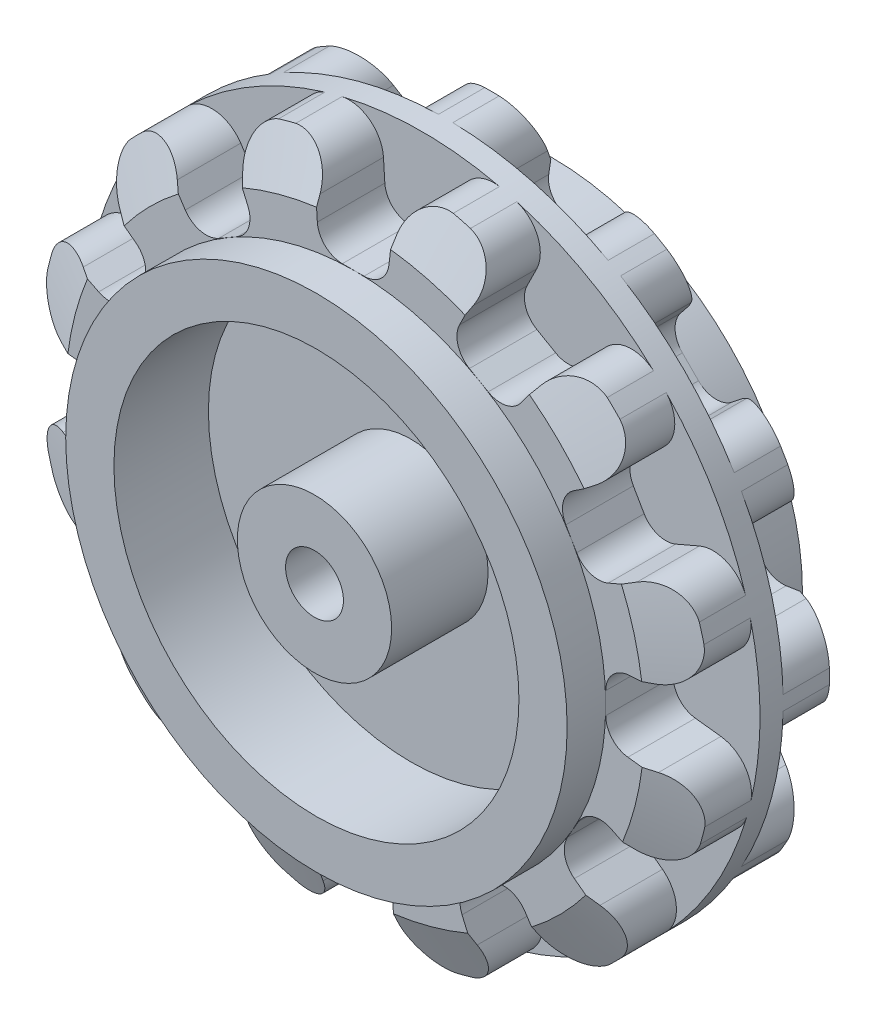
SolidWorks part; units mm, degrees
ref_plane "Plan de face" through (0, 0, 0) normal (0, 0, 1) x (1, 0, 0)
ref_plane "Plan de dessus" through (0, 0, 0) normal (0, 1, 0) x (1, 0, 0)
ref_plane "Plan de droite" through (0, 0, 0) normal (1, 0, 0) x (0, 0, -1)
sketch "Esquisse2" plane through (0, 0, 0) normal (0, 1, 0) x (1, 0, 0)
  line L0 (0, 0) -> (0, 3425.2641) construction
  line L1 (-17.5, -1.958) -> (-1.5, -1.958) construction
  line L2 (-17.5, -4.958) -> (-17.5, 1.042)
  line L3 (-17.5, 1.042) -> (-15, 2.142)
  line L4 (-15, 2.142) -> (-13, 2.142)
  line L5 (-13, 2.142) -> (-13, 4.142)
  line L6 (-13, 4.142) -> (-10.5, 4.142)
  line L7 (-10.5, 4.142) -> (-10.5, -0.758)
  line L8 (-10.5, -0.758) -> (-4, -0.758)
  line L9 (-1.5, -0.758) -> (-1.5, -3.158)
  line L10 (-10.5, -3.158) -> (-4, -3.158)
  line L11 (-10.5, -8.058) -> (-10.5, -3.158)
  line L12 (-13, -8.058) -> (-10.5, -8.058)
  line L13 (-13, -6.058) -> (-13, -8.058)
  line L14 (-15, -6.058) -> (-13, -6.058)
  line L15 (-17.5, -4.958) -> (-15, -6.058)
  line L16 (-1.5, -0.758) -> (-1.5, -0.058)
  line L17 (-1.5, -0.058) -> (-4, -0.058)
  line L18 (-4, -0.058) -> (-4, -0.758)
  line L19 (-1.5, -3.158) -> (-1.5, -8.158)
  line L20 (-1.5, -8.158) -> (-4, -8.158)
  line L21 (-4, -8.158) -> (-4, -3.158)
  dimension "D1" = 1.5
  dimension "D2" = 10.5
  dimension "D3" = 17.5
  dimension "D4" = 2
  dimension "D5" = 2.5
  dimension "D6" = 1.2
  dimension "D7" = 3
  dimension "D8" = 4.1
  dimension "D9" = 2
  dimension "D10" = 4.9
  dimension "D11" = 2.5
  dimension "D12" = 0.7
  dimension "D13" = 2.5
  dimension "D14" = 5
revolve "Révolution1" add sketch "Esquisse2" angle 360 about L0
sketch "Esquisse3" plane through (0, 0, 6.058) normal (0, 0, 1) x (1, 0, 0)
  line L0 (0, 0) -> (0, 50000) construction
  line L1 (0, 0) -> (4.5293, 16.9037) construction
  line L2 (0, 0) -> (-4.5293, 16.9037) construction
  line L3 (-0.655, 13) -> (0.4677, 13)
  line L4 (-2.3132, 17.3932) -> (2.1868, 17.3932) construction
  line L5 (-4.5293, 16.9037) -> (-4.2854, 16.9691)
  line L6 (4.5293, 16.9037) -> (4.1678, 17.0006)
  line L7 (-1.9525, 14.2186) -> (-2.023, 15.3431)
  line L8 (1.9142, 15.4718) -> (1.7588, 14.1484)
  line L9 (-4.9465, 18.4605) -> (-12940.9449, 48296.2637) construction
  line L10 (5.9327, 11.5858) -> (6.905, 11.0245)
  line L11 (4.5293, 16.9037) -> (4.7733, 16.8383)
  line L12 (-4.9465, 18.4605) -> (4.9465, 18.4605)
  line L13 (-4.5293, 16.9037) -> (-4.9465, 18.4605)
  line L14 (-4.5293, 16.9037) -> (-2.1608, 17.5384) construction
  line L15 (4.5293, 16.9037) -> (2.2281, 17.5203) construction
  line L16 (2.2281, 17.5203) -> (1.9142, 15.4718) construction
  line L17 (-2.023, 15.3431) -> (-2.1608, 17.5384) construction
  line L18 (12.3744, 12.3744) -> (12.1097, 12.639)
  line L19 (5.4184, 13.2899) -> (5.9196, 14.2991)
  line L20 (9.3937, 12.4419) -> (8.5974, 11.3735)
  line L21 (4.9465, 18.4605) -> (13.514, 13.514)
  line L22 (4.9465, 18.4605) -> (12940.9192, 48296.1679) construction
  line L23 (4.5293, 16.9037) -> (4.9465, 18.4605)
  line L24 (4.5293, 16.9037) -> (4.9465, 18.4605)
  line L25 (12.3744, 12.3744) -> (13.514, 13.514)
  line L26 (10.9308, 7.0673) -> (11.4922, 6.095)
  line L27 (12.3744, 12.3744) -> (12.5529, 12.1958)
  line L28 (16.9037, 4.5293) -> (16.8068, 4.8908)
  line L29 (11.3374, 8.8002) -> (12.276, 9.4236)
  line L30 (14.3561, 6.0781) -> (13.1323, 5.551)
  line L31 (13.514, 13.514) -> (18.4605, 4.9465)
  line L32 (12.3744, 12.3744) -> (13.514, 13.514)
  line L33 (16.9037, 4.5293) -> (18.4605, 4.9465)
  line L34 (13, 0.655) -> (13, -0.4677)
  line L35 (16.9037, 4.5293) -> (16.9691, 4.2854)
  line L36 (16.9037, -4.5293) -> (17.0006, -4.1678)
  line L37 (14.2186, 1.9525) -> (15.3431, 2.023)
  line L38 (15.4718, -1.9142) -> (14.1484, -1.7588)
  line L39 (18.4605, 4.9465) -> (18.4605, -4.9465)
  line L40 (16.9037, 4.5293) -> (18.4605, 4.9465)
  line L41 (16.9037, -4.5293) -> (18.4605, -4.9465)
  line L42 (11.5858, -5.9327) -> (11.0245, -6.905)
  line L43 (16.9037, -4.5293) -> (16.8383, -4.7733)
  line L44 (12.3744, -12.3744) -> (12.639, -12.1097)
  line L45 (13.2899, -5.4184) -> (14.2991, -5.9196)
  line L46 (12.4419, -9.3937) -> (11.3735, -8.5974)
  line L47 (18.4605, -4.9465) -> (13.514, -13.514)
  line L48 (16.9037, -4.5293) -> (18.4605, -4.9465)
  line L49 (12.3744, -12.3744) -> (13.514, -13.514)
  line L50 (7.0673, -10.9308) -> (6.095, -11.4922)
  line L51 (12.3744, -12.3744) -> (12.1958, -12.5529)
  line L52 (4.5293, -16.9037) -> (4.8908, -16.8068)
  line L53 (8.8002, -11.3374) -> (9.4236, -12.276)
  line L54 (6.0781, -14.3561) -> (5.551, -13.1323)
  line L55 (13.514, -13.514) -> (4.9465, -18.4605)
  line L56 (12.3744, -12.3744) -> (13.514, -13.514)
  line L57 (4.5293, -16.9037) -> (4.9465, -18.4605)
  line L58 (0.655, -13) -> (-0.4677, -13)
  line L59 (4.5293, -16.9037) -> (4.2854, -16.9691)
  line L60 (-4.5293, -16.9037) -> (-4.1678, -17.0006)
  line L61 (1.9525, -14.2186) -> (2.023, -15.3431)
  line L62 (-1.9142, -15.4718) -> (-1.7588, -14.1484)
  line L63 (4.9465, -18.4605) -> (-4.9465, -18.4605)
  line L64 (4.5293, -16.9037) -> (4.9465, -18.4605)
  line L65 (-4.5293, -16.9037) -> (-4.9465, -18.4605)
  line L66 (-5.9327, -11.5858) -> (-6.905, -11.0245)
  line L67 (-4.5293, -16.9037) -> (-4.7733, -16.8383)
  line L68 (-12.3744, -12.3744) -> (-12.1097, -12.639)
  line L69 (-5.4184, -13.2899) -> (-5.9196, -14.2991)
  line L70 (-9.3937, -12.4419) -> (-8.5974, -11.3735)
  line L71 (-4.9465, -18.4605) -> (-13.514, -13.514)
  line L72 (-4.5293, -16.9037) -> (-4.9465, -18.4605)
  line L73 (-12.3744, -12.3744) -> (-13.514, -13.514)
  line L74 (-10.9308, -7.0673) -> (-11.4922, -6.095)
  line L75 (-12.3744, -12.3744) -> (-12.5529, -12.1958)
  line L76 (-16.9037, -4.5293) -> (-16.8068, -4.8908)
  line L77 (-11.3374, -8.8002) -> (-12.276, -9.4236)
  line L78 (-14.3561, -6.0781) -> (-13.1323, -5.551)
  line L79 (-13.514, -13.514) -> (-18.4605, -4.9465)
  line L80 (-12.3744, -12.3744) -> (-13.514, -13.514)
  line L81 (-16.9037, -4.5293) -> (-18.4605, -4.9465)
  line L82 (-13, -0.655) -> (-13, 0.4677)
  line L83 (-16.9037, -4.5293) -> (-16.9691, -4.2854)
  line L84 (-16.9037, 4.5293) -> (-17.0006, 4.1678)
  line L85 (-14.2186, -1.9525) -> (-15.3431, -2.023)
  line L86 (-15.4718, 1.9142) -> (-14.1484, 1.7588)
  line L87 (-18.4605, -4.9465) -> (-18.4605, 4.9465)
  line L88 (-16.9037, -4.5293) -> (-18.4605, -4.9465)
  line L89 (-16.9037, 4.5293) -> (-18.4605, 4.9465)
  line L90 (-11.5858, 5.9327) -> (-11.0245, 6.905)
  line L91 (-16.9037, 4.5293) -> (-16.8383, 4.7733)
  line L92 (-12.3744, 12.3744) -> (-12.639, 12.1097)
  line L93 (-13.2899, 5.4184) -> (-14.2991, 5.9196)
  line L94 (-12.4419, 9.3937) -> (-11.3735, 8.5974)
  line L95 (-18.4605, 4.9465) -> (-13.514, 13.514)
  line L96 (-16.9037, 4.5293) -> (-18.4605, 4.9465)
  line L97 (-12.3744, 12.3744) -> (-13.514, 13.514)
  line L98 (-7.0673, 10.9308) -> (-6.095, 11.4922)
  line L99 (-12.3744, 12.3744) -> (-12.1958, 12.5529)
  line L100 (-4.5293, 16.9037) -> (-4.8908, 16.8068)
  line L101 (-8.8002, 11.3374) -> (-9.4236, 12.276)
  line L102 (-6.0781, 14.3561) -> (-5.551, 13.1323)
  line L103 (-13.514, 13.514) -> (-4.9465, 18.4605)
  line L104 (-12.3744, 12.3744) -> (-13.514, 13.514)
  line L105 (-4.5293, 16.9037) -> (-4.9465, 18.4605)
  arc A0 (4.1678, 17.0006) -> (1.9142, 15.4718) centre (3.7019, 15.2619) ccw
  arc A1 (-2.023, 15.3431) -> (-4.2854, 16.9691) centre (-3.8195, 15.2304) ccw
  circle A4 centre (0, 0) radius 15 construction
  arc A5 (12.1097, 12.639) -> (9.3937, 12.4419) centre (10.8369, 11.3662) ccw
  arc A6 (5.9196, 14.2991) -> (4.7733, 16.8383) centre (4.3074, 15.0997) ccw
  arc A7 (8.5974, 11.3735) -> (6.905, 11.0245) centre (7.555, 12.1503) cw
  arc A8 (5.9327, 11.5858) -> (5.4184, 13.2899) centre (6.5827, 12.7117) cw
  arc A9 (16.8068, 4.8908) -> (14.3561, 6.0781) centre (15.0682, 4.425) ccw
  arc A10 (12.276, 9.4236) -> (12.5529, 12.1958) centre (11.2802, 10.923) ccw
  arc A11 (13.1323, 5.551) -> (11.4922, 6.095) centre (12.618, 6.745) cw
  arc A12 (10.9308, 7.0673) -> (11.3374, 8.8002) centre (12.0566, 7.7173) cw
  arc A13 (17.0006, -4.1678) -> (15.4718, -1.9142) centre (15.2619, -3.7019) ccw
  arc A14 (15.3431, 2.023) -> (16.9691, 4.2854) centre (15.2304, 3.8195) ccw
  arc A15 (14.1484, -1.7588) -> (13, -0.4677) centre (14.3, -0.4677) cw
  arc A16 (13, 0.655) -> (14.2186, 1.9525) centre (14.3, 0.655) cw
  arc A17 (12.639, -12.1097) -> (12.4419, -9.3937) centre (11.3662, -10.8369) ccw
  arc A18 (14.2991, -5.9196) -> (16.8383, -4.7733) centre (15.0997, -4.3074) ccw
  arc A19 (11.3735, -8.5974) -> (11.0245, -6.905) centre (12.1503, -7.555) cw
  arc A20 (11.5858, -5.9327) -> (13.2899, -5.4184) centre (12.7117, -6.5827) cw
  arc A21 (4.8908, -16.8068) -> (6.0781, -14.3561) centre (4.425, -15.0682) ccw
  arc A22 (9.4236, -12.276) -> (12.1958, -12.5529) centre (10.923, -11.2802) ccw
  arc A23 (5.551, -13.1323) -> (6.095, -11.4922) centre (6.745, -12.618) cw
  arc A24 (7.0673, -10.9308) -> (8.8002, -11.3374) centre (7.7173, -12.0566) cw
  arc A25 (-4.1678, -17.0006) -> (-1.9142, -15.4718) centre (-3.7019, -15.2619) ccw
  arc A26 (2.023, -15.3431) -> (4.2854, -16.9691) centre (3.8195, -15.2304) ccw
  arc A27 (-1.7588, -14.1484) -> (-0.4677, -13) centre (-0.4677, -14.3) cw
  arc A28 (0.655, -13) -> (1.9525, -14.2186) centre (0.655, -14.3) cw
  arc A29 (-12.1097, -12.639) -> (-9.3937, -12.4419) centre (-10.8369, -11.3662) ccw
  arc A30 (-5.9196, -14.2991) -> (-4.7733, -16.8383) centre (-4.3074, -15.0997) ccw
  arc A31 (-8.5974, -11.3735) -> (-6.905, -11.0245) centre (-7.555, -12.1503) cw
  arc A32 (-5.9327, -11.5858) -> (-5.4184, -13.2899) centre (-6.5827, -12.7117) cw
  arc A33 (-16.8068, -4.8908) -> (-14.3561, -6.0781) centre (-15.0682, -4.425) ccw
  arc A34 (-12.276, -9.4236) -> (-12.5529, -12.1958) centre (-11.2802, -10.923) ccw
  arc A35 (-13.1323, -5.551) -> (-11.4922, -6.095) centre (-12.618, -6.745) cw
  arc A36 (-10.9308, -7.0673) -> (-11.3374, -8.8002) centre (-12.0566, -7.7173) cw
  arc A37 (-17.0006, 4.1678) -> (-15.4718, 1.9142) centre (-15.2619, 3.7019) ccw
  arc A38 (-15.3431, -2.023) -> (-16.9691, -4.2854) centre (-15.2304, -3.8195) ccw
  arc A39 (-14.1484, 1.7588) -> (-13, 0.4677) centre (-14.3, 0.4677) cw
  arc A40 (-13, -0.655) -> (-14.2186, -1.9525) centre (-14.3, -0.655) cw
  arc A41 (-12.639, 12.1097) -> (-12.4419, 9.3937) centre (-11.3662, 10.8369) ccw
  arc A42 (-14.2991, 5.9196) -> (-16.8383, 4.7733) centre (-15.0997, 4.3074) ccw
  arc A43 (-11.3735, 8.5974) -> (-11.0245, 6.905) centre (-12.1503, 7.555) cw
  arc A44 (-11.5858, 5.9327) -> (-13.2899, 5.4184) centre (-12.7117, 6.5827) cw
  arc A45 (-4.8908, 16.8068) -> (-6.0781, 14.3561) centre (-4.425, 15.0682) ccw
  arc A46 (-9.4236, 12.276) -> (-12.1958, 12.5529) centre (-10.923, 11.2802) ccw
  arc A47 (-5.551, 13.1323) -> (-6.095, 11.4922) centre (-6.745, 12.618) cw
  arc A48 (1.7588, 14.1484) -> (0.4677, 13) centre (0.4677, 14.3) cw
  arc A49 (-0.655, 13) -> (-1.9525, 14.2186) centre (-0.655, 14.3) cw
  arc A50 (-7.0673, 10.9308) -> (-8.8002, 11.3374) centre (-7.7173, 12.0566) cw
  point P8 (0, 13)
  point P11 (0, 17.33)
  point P24 (1.624, 13)
  point P30 (-1.876, 13)
  point P35 (6.5, 11.2583)
  point P52 (11.2583, 6.5)
  point P69 (13, 0)
  point P86 (11.2583, -6.5)
  point P103 (6.5, -11.2583)
  point P120 (0, -13)
  point P137 (-6.5, -11.2583)
  point P154 (-11.2583, -6.5)
  point P171 (-13, 0)
  point P188 (-11.2583, 6.5)
  point P205 (-6.5, 11.2583)
  point P221 (0, 0)
  point P273 (-0.0632, 0.0632)
  dimension "D4" = 1.8
  dimension "D11" = 1.3
  dimension "D1" = 15
  dimension "D2" = 15
  dimension "D3" = 90
  dimension "D5" = 4.5
  dimension "D6" = 17.5
  dimension "D7" = 17.5
  dimension "D8" = 12
  dimension "D10" = 3.5
extrude "Enlèv. mat.-Extru.2" cut sketch "Esquisse3" against normal blind 3.5
sketch "Esquisse4" plane through (0, 0, -2.142) normal (0, 0, -1) x (-1, 0, 0)
  line L0 (0, 0) -> (0, 50000) construction
  line L1 (0, 0) -> (-12940.9523, 48296.2913) construction
  line L2 (0, 0) -> (-25000, 43301.2702) construction
  line L3 (-3.9354, 12.4041) -> (-2.7939, 12.71)
  line L4 (-8.75, 15.1554) -> (-8.5302, 15.2824)
  line L5 (0, 17.5) -> (-0.2539, 17.5)
  line L6 (-6.6638, 16.1765) -> (-2.3172, 17.3412)
  line L7 (-5.4809, 13.1822) -> (-5.9561, 14.3849)
  line L8 (-1.8445, 14.1565) -> (-2.0343, 15.4357)
  line L9 (-8.75, 15.1554) -> (-9.8936, 17.1362)
  line L10 (-9.8936, 17.1362) -> (0, 19.7872)
  line L11 (0, 19.7872) -> (0, 17.5)
  line L12 (2.7939, 12.71) -> (3.9354, 12.4041)
  line L13 (0, 17.5) -> (0.2539, 17.5)
  line L14 (8.75, 15.1554) -> (8.5302, 15.2824)
  line L15 (1.8445, 14.1565) -> (2.0343, 15.4357)
  line L16 (5.4809, 13.1822) -> (5.9561, 14.3849)
  line L17 (0, 17.5) -> (0, 19.7872)
  line L18 (0, 19.7872) -> (9.8936, 17.1362)
  line L19 (9.8936, 17.1362) -> (8.75, 15.1554)
  line L20 (8.7746, 9.6102) -> (9.6102, 8.7746)
  line L21 (8.75, 15.1554) -> (8.9698, 15.0285)
  line L22 (15.1554, 8.75) -> (15.0285, 8.9698)
  line L23 (8.6756, 11.3377) -> (9.4796, 12.3505)
  line L24 (11.3377, 8.6756) -> (12.3505, 9.4796)
  line L25 (8.75, 15.1554) -> (9.8936, 17.1362)
  line L26 (9.8936, 17.1362) -> (17.1362, 9.8936)
  line L27 (17.1362, 9.8936) -> (15.1554, 8.75)
  line L28 (12.4041, 3.9354) -> (12.71, 2.7939)
  line L29 (15.1554, 8.75) -> (15.2824, 8.5302)
  line L30 (17.5, 0) -> (17.5, 0.2539)
  line L31 (13.1822, 5.4809) -> (14.3849, 5.9561)
  line L32 (14.1565, 1.8445) -> (15.4357, 2.0343)
  line L33 (15.1554, 8.75) -> (17.1362, 9.8936)
  line L34 (17.1362, 9.8936) -> (19.7872, 0)
  line L35 (19.7872, 0) -> (17.5, 0)
  line L36 (12.71, -2.7939) -> (12.4041, -3.9354)
  line L37 (17.5, 0) -> (17.5, -0.2539)
  line L38 (15.1554, -8.75) -> (15.2824, -8.5302)
  line L39 (14.1565, -1.8445) -> (15.4357, -2.0343)
  line L40 (13.1822, -5.4809) -> (14.3849, -5.9561)
  line L41 (17.5, 0) -> (19.7872, 0)
  line L42 (19.7872, 0) -> (17.1362, -9.8936)
  line L43 (17.1362, -9.8936) -> (15.1554, -8.75)
  line L44 (9.6102, -8.7746) -> (8.7746, -9.6102)
  line L45 (15.1554, -8.75) -> (15.0285, -8.9698)
  line L46 (8.75, -15.1554) -> (8.9698, -15.0285)
  line L47 (11.3377, -8.6756) -> (12.3505, -9.4796)
  line L48 (8.6756, -11.3377) -> (9.4796, -12.3505)
  line L49 (15.1554, -8.75) -> (17.1362, -9.8936)
  line L50 (17.1362, -9.8936) -> (9.8936, -17.1362)
  line L51 (9.8936, -17.1362) -> (8.75, -15.1554)
  line L52 (3.9354, -12.4041) -> (2.7939, -12.71)
  line L53 (8.75, -15.1554) -> (8.5302, -15.2824)
  line L54 (0, -17.5) -> (0.2539, -17.5)
  line L55 (5.4809, -13.1822) -> (5.9561, -14.3849)
  line L56 (1.8445, -14.1565) -> (2.0343, -15.4357)
  line L57 (8.75, -15.1554) -> (9.8936, -17.1362)
  line L58 (9.8936, -17.1362) -> (0, -19.7872)
  line L59 (0, -19.7872) -> (0, -17.5)
  line L60 (-2.7939, -12.71) -> (-3.9354, -12.4041)
  line L61 (0, -17.5) -> (-0.2539, -17.5)
  line L62 (-8.75, -15.1554) -> (-8.5302, -15.2824)
  line L63 (-1.8445, -14.1565) -> (-2.0343, -15.4357)
  line L64 (-5.4809, -13.1822) -> (-5.9561, -14.3849)
  line L65 (0, -17.5) -> (0, -19.7872)
  line L66 (0, -19.7872) -> (-9.8936, -17.1362)
  line L67 (-9.8936, -17.1362) -> (-8.75, -15.1554)
  line L68 (-8.7746, -9.6102) -> (-9.6102, -8.7746)
  line L69 (-8.75, -15.1554) -> (-8.9698, -15.0285)
  line L70 (-15.1554, -8.75) -> (-15.0285, -8.9698)
  line L71 (-8.6756, -11.3377) -> (-9.4796, -12.3505)
  line L72 (-11.3377, -8.6756) -> (-12.3505, -9.4796)
  line L73 (-8.75, -15.1554) -> (-9.8936, -17.1362)
  line L74 (-9.8936, -17.1362) -> (-17.1362, -9.8936)
  line L75 (-17.1362, -9.8936) -> (-15.1554, -8.75)
  line L76 (-12.4041, -3.9354) -> (-12.71, -2.7939)
  line L77 (-15.1554, -8.75) -> (-15.2824, -8.5302)
  line L78 (-17.5, 0) -> (-17.5, -0.2539)
  line L79 (-13.1822, -5.4809) -> (-14.3849, -5.9561)
  line L80 (-14.1565, -1.8445) -> (-15.4357, -2.0343)
  line L81 (-15.1554, -8.75) -> (-17.1362, -9.8936)
  line L82 (-17.1362, -9.8936) -> (-19.7872, 0)
  line L83 (-19.7872, 0) -> (-17.5, 0)
  line L84 (-12.71, 2.7939) -> (-12.4041, 3.9354)
  line L85 (-17.5, 0) -> (-17.5, 0.2539)
  line L86 (-15.1554, 8.75) -> (-15.2824, 8.5302)
  line L87 (-14.1565, 1.8445) -> (-15.4357, 2.0343)
  line L88 (-13.1822, 5.4809) -> (-14.3849, 5.9561)
  line L89 (-17.5, 0) -> (-19.7872, 0)
  line L90 (-19.7872, 0) -> (-17.1362, 9.8936)
  line L91 (-17.1362, 9.8936) -> (-15.1554, 8.75)
  line L92 (-9.6102, 8.7746) -> (-8.7746, 9.6102)
  line L93 (-15.1554, 8.75) -> (-15.0285, 8.9698)
  line L94 (-8.75, 15.1554) -> (-8.9698, 15.0285)
  line L95 (-11.3377, 8.6756) -> (-12.3505, 9.4796)
  line L96 (-8.6756, 11.3377) -> (-9.4796, 12.3505)
  line L97 (-15.1554, 8.75) -> (-17.1362, 9.8936)
  line L98 (-17.1362, 9.8936) -> (-9.8936, 17.1362)
  line L99 (-9.8936, 17.1362) -> (-8.75, 15.1554)
  circle A0 centre (0, 0) radius 13 construction
  circle A1 centre (0, 0) radius 17.5 construction
  arc A2 (-1.8445, 14.1565) -> (-2.7939, 12.71) centre (-3.1304, 13.9657) cw
  arc A3 (-3.9354, 12.4041) -> (-5.4809, 13.1822) centre (-4.2718, 13.6598) cw
  arc A4 (-0.2539, 17.5) -> (-2.0343, 15.4357) centre (-0.2539, 15.7) ccw
  arc A5 (-5.9561, 14.3849) -> (-8.5302, 15.2824) centre (-7.6302, 13.7235) ccw
  arc A6 (5.4809, 13.1822) -> (3.9354, 12.4041) centre (4.2718, 13.6598) cw
  arc A7 (2.7939, 12.71) -> (1.8445, 14.1565) centre (3.1304, 13.9657) cw
  arc A8 (8.5302, 15.2824) -> (5.9561, 14.3849) centre (7.6302, 13.7235) ccw
  arc A9 (2.0343, 15.4357) -> (0.2539, 17.5) centre (0.2539, 15.7) ccw
  arc A10 (11.3377, 8.6756) -> (9.6102, 8.7746) centre (10.5294, 9.6938) cw
  arc A11 (8.7746, 9.6102) -> (8.6756, 11.3377) centre (9.6938, 10.5294) cw
  arc A12 (15.0285, 8.9698) -> (12.3505, 9.4796) centre (13.4697, 8.0698) ccw
  arc A13 (9.4796, 12.3505) -> (8.9698, 15.0285) centre (8.0698, 13.4697) ccw
  arc A14 (14.1565, 1.8445) -> (12.71, 2.7939) centre (13.9657, 3.1304) cw
  arc A15 (12.4041, 3.9354) -> (13.1822, 5.4809) centre (13.6598, 4.2718) cw
  arc A16 (17.5, 0.2539) -> (15.4357, 2.0343) centre (15.7, 0.2539) ccw
  arc A17 (14.3849, 5.9561) -> (15.2824, 8.5302) centre (13.7235, 7.6302) ccw
  arc A18 (13.1822, -5.4809) -> (12.4041, -3.9354) centre (13.6598, -4.2718) cw
  arc A19 (12.71, -2.7939) -> (14.1565, -1.8445) centre (13.9657, -3.1304) cw
  arc A20 (15.2824, -8.5302) -> (14.3849, -5.9561) centre (13.7235, -7.6302) ccw
  arc A21 (15.4357, -2.0343) -> (17.5, -0.2539) centre (15.7, -0.2539) ccw
  arc A22 (8.6756, -11.3377) -> (8.7746, -9.6102) centre (9.6938, -10.5294) cw
  arc A23 (9.6102, -8.7746) -> (11.3377, -8.6756) centre (10.5294, -9.6938) cw
  arc A24 (8.9698, -15.0285) -> (9.4796, -12.3505) centre (8.0698, -13.4697) ccw
  arc A25 (12.3505, -9.4796) -> (15.0285, -8.9698) centre (13.4697, -8.0698) ccw
  arc A26 (1.8445, -14.1565) -> (2.7939, -12.71) centre (3.1304, -13.9657) cw
  arc A27 (3.9354, -12.4041) -> (5.4809, -13.1822) centre (4.2718, -13.6598) cw
  arc A28 (0.2539, -17.5) -> (2.0343, -15.4357) centre (0.2539, -15.7) ccw
  arc A29 (5.9561, -14.3849) -> (8.5302, -15.2824) centre (7.6302, -13.7235) ccw
  arc A30 (-5.4809, -13.1822) -> (-3.9354, -12.4041) centre (-4.2718, -13.6598) cw
  arc A31 (-2.7939, -12.71) -> (-1.8445, -14.1565) centre (-3.1304, -13.9657) cw
  arc A32 (-8.5302, -15.2824) -> (-5.9561, -14.3849) centre (-7.6302, -13.7235) ccw
  arc A33 (-2.0343, -15.4357) -> (-0.2539, -17.5) centre (-0.2539, -15.7) ccw
  arc A34 (-11.3377, -8.6756) -> (-9.6102, -8.7746) centre (-10.5294, -9.6938) cw
  arc A35 (-8.7746, -9.6102) -> (-8.6756, -11.3377) centre (-9.6938, -10.5294) cw
  arc A36 (-15.0285, -8.9698) -> (-12.3505, -9.4796) centre (-13.4697, -8.0698) ccw
  arc A37 (-9.4796, -12.3505) -> (-8.9698, -15.0285) centre (-8.0698, -13.4697) ccw
  arc A38 (-14.1565, -1.8445) -> (-12.71, -2.7939) centre (-13.9657, -3.1304) cw
  arc A39 (-12.4041, -3.9354) -> (-13.1822, -5.4809) centre (-13.6598, -4.2718) cw
  arc A40 (-17.5, -0.2539) -> (-15.4357, -2.0343) centre (-15.7, -0.2539) ccw
  arc A41 (-14.3849, -5.9561) -> (-15.2824, -8.5302) centre (-13.7235, -7.6302) ccw
  arc A42 (-13.1822, 5.4809) -> (-12.4041, 3.9354) centre (-13.6598, 4.2718) cw
  arc A43 (-12.71, 2.7939) -> (-14.1565, 1.8445) centre (-13.9657, 3.1304) cw
  arc A44 (-15.2824, 8.5302) -> (-14.3849, 5.9561) centre (-13.7235, 7.6302) ccw
  arc A45 (-15.4357, 2.0343) -> (-17.5, 0.2539) centre (-15.7, 0.2539) ccw
  arc A46 (-8.6756, 11.3377) -> (-8.7746, 9.6102) centre (-9.6938, 10.5294) cw
  arc A47 (-9.6102, 8.7746) -> (-11.3377, 8.6756) centre (-10.5294, 9.6938) cw
  arc A48 (-8.9698, 15.0285) -> (-9.4796, 12.3505) centre (-8.0698, 13.4697) ccw
  arc A49 (-12.3505, 9.4796) -> (-15.0285, 8.9698) centre (-13.4697, 8.0698) ccw
  point P10 (-3.3646, 12.557)
  point P21 (-4.4905, 16.7588)
  point P23 (-1.6743, 13.01)
  point P26 (-5.055, 12.1041)
  point P38 (3.3646, 12.557)
  point P55 (9.1924, 9.1924)
  point P72 (12.557, 3.3646)
  point P89 (12.557, -3.3646)
  point P106 (9.1924, -9.1924)
  point P123 (3.3646, -12.557)
  point P140 (-3.3646, -12.557)
  point P157 (-9.1924, -9.1924)
  point P174 (-12.557, -3.3646)
  point P191 (-12.557, 3.3646)
  point P208 (-9.1924, 9.1924)
  point P223 (0, 0)
  dimension "D10" = 1.3
  dimension "D8" = 1.8
  dimension "D1" = 15
  dimension "D2" = 15
  dimension "D3" = 3.5
  dimension "D4" = 13
  dimension "D5" = 17.5
  dimension "D6" = 17.5
  dimension "D7" = 90
  dimension "D9" = 17.35
  dimension "D11" = 12
extrude "Enlèv. mat.-Extru.3" cut sketch "Esquisse4" against normal blind 3.5 contours L10 L11 L5 A4 L8 A2 L3 A3 L7 A5 L4 L9 | L98 L99 L94 A48 L96 A46 L92 A47 L95 A49 L93 L97 | L90 L91 L86 A44 L88 A42 L84 A43 L87 A45 L85 L89 | L82 L83 L78 A40 L80 A38 L76 A39 L79 A41 L77 L81 | L74 L75 L70 A36 L72 A34 L68 A35 L71 A37 L69 L73 | L66 L67 L62 A32 L64 A30 L60 A31 L63 A33 L61 L65 | L58 L59 L54 A28 L56 A26 L52 A27 L55 A29 L53 L57 | L50 L51 L46 A24 L48 A22 L44 A23 L47 A25 L45 L49 | L42 L43 L38 A20 L40 A18 L36 A19 L39 A21 L37 L41 | L34 L35 L30 A16 L32 A14 L28 A15 L31 A17 L29 L33 | L26 L27 L22 A12 L24 A10 L20 A11 L23 A13 L21 L25 | L18 L19 L14 A8 L16 A6 L12 A7 L15 A9 L13 L17
